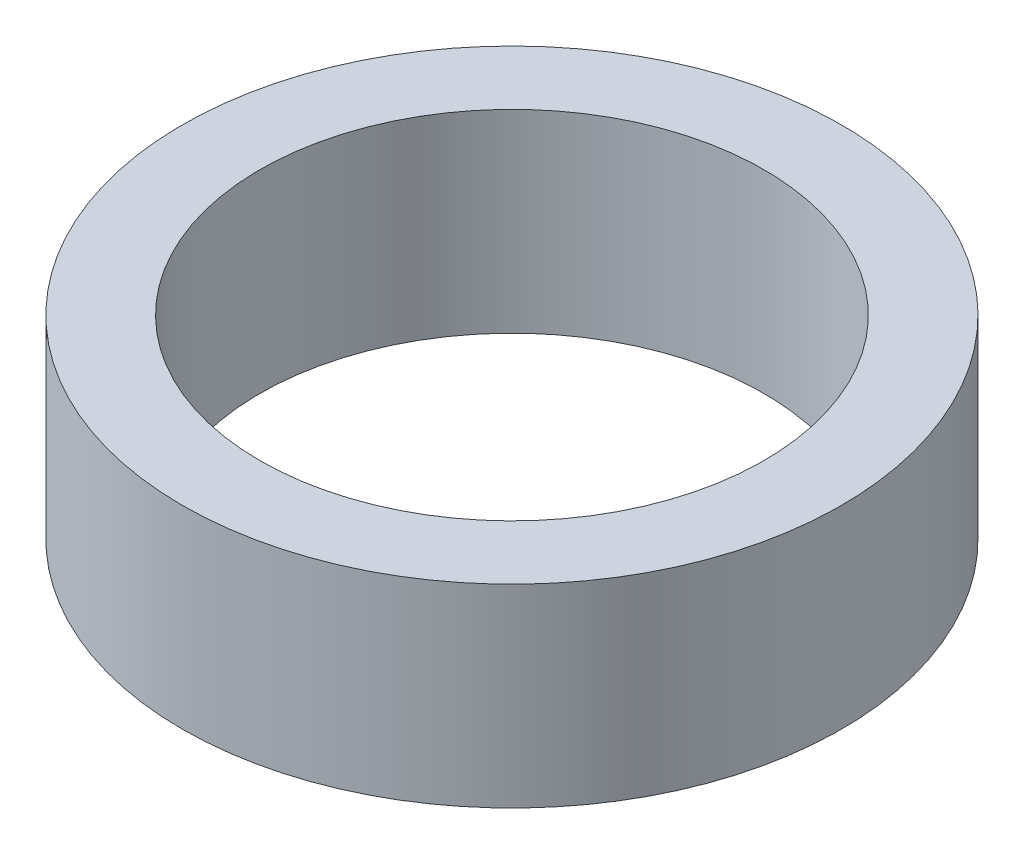
SolidWorks part; units mm, degrees
ref_plane "Front Plane" through (0, 0, 0) normal (0, 0, 1) x (1, 0, 0)
ref_plane "Top Plane" through (0, 0, 0) normal (0, 1, 0) x (1, 0, 0)
ref_plane "Right Plane" through (0, 0, 0) normal (1, 0, 0) x (0, 0, -1)
sketch "Sketch1" plane through (0, 0, 0) normal (0, 1, 0) x (1, 0, 0)
  circle A0 centre (0, 0) radius 42.5
  dimension "FLANGE_OD" = 85
extrude "Boss-Extrude1" add sketch "Sketch1" along normal blind 25
sketch "Sketch2" plane through (0, 0, 0) normal (0, 1, 0) x (1, 0, 0)
  circle A0 centre (0, 0) radius 32.5
  dimension "BORE_D" = 65
extrude "Cut-Extrude1" cut sketch "Sketch2" along normal through all
sketch "Sketch3" plane through (0, 25, 0) normal (0, 1, 0) x (1, 0, 0)
  circle A0 centre (0, 0) radius 18.9029 construction
  circle A1 centre (-18.9029, 0) radius 1.7067
  dimension "BOLT_D" = 3.4135
  dimension "BOLT_PCD" = 37.8059
extrude "Cut-Extrude2" cut sketch "Sketch3" against normal blind 17.999 rebuild error yes
pattern_circular "CirPattern1" count 4 over 360 rebuild error yes
